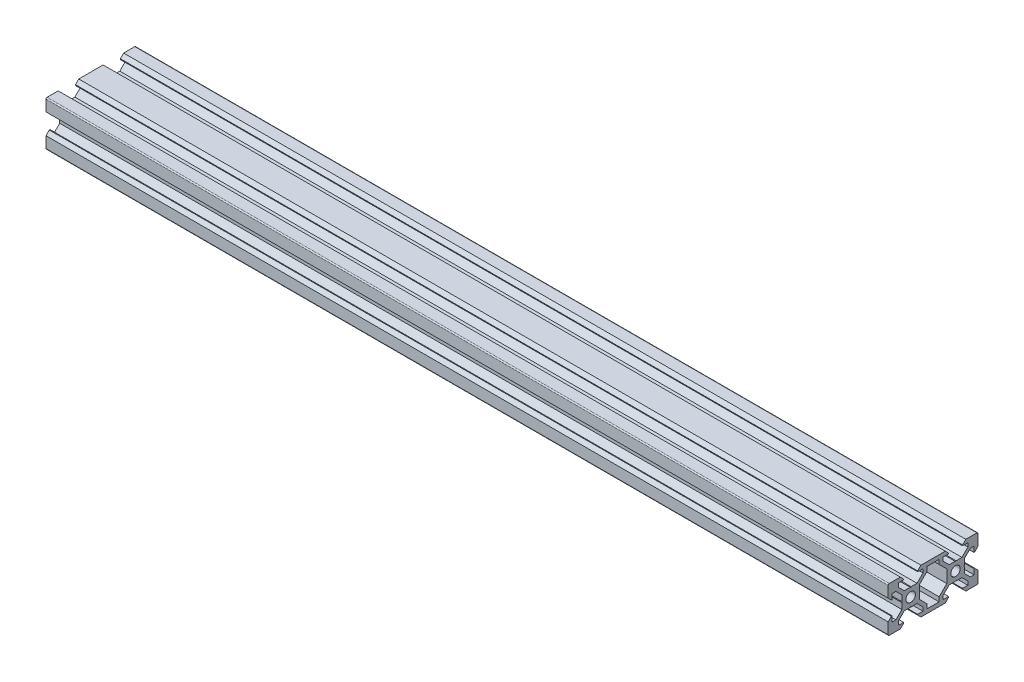
SolidWorks part; units mm, degrees
material "6061-T6 (SS)"
ref_plane "Top" through (0, 0, 0) normal (0, 0, 1) x (1, 0, 0)
ref_plane "Front" through (0, 0, 0) normal (0, 1, 0) x (1, 0, 0)
ref_plane "Right" through (0, 0, 0) normal (1, 0, 0) x (0, 0, -1)
sketch "Profile Sketch" plane through (0, 0, 0) normal (1, 0, 0) x (0, 0, -1)
  line L0 (5.42, 10) -> (-5.42, 10)
  line L1 (-4.5, 8.2) -> (-4.5, 6.56)
  line L2 (-4.5, 6.56) -> (-7.16, 3.9)
  line L3 (-7.16, 3.9) -> (-9.79, 3.9)
  line L4 (-9.79, 3.9) -> (-10, 3.69)
  line L5 (2.7, 8.2) -> (-2.7, 8.2)
  line L6 (-2.7, 8.2) -> (-2.7, 6.2387)
  line L7 (-2.7, 6.2387) -> (-6.1, 2.8387)
  line L8 (-6.1, 2.8387) -> (-6.1, -0.21)
  line L9 (-6.875, 8.545) -> (-6.875, 8.2)
  line L10 (-6.875, 8.2) -> (-4.5, 8.2)
  line L11 (-6.875, 8.545) -> (-5.42, 10)
  line L12 (0, -10) -> (0, 10) construction
  line L13 (-20, 0) -> (20, 0) construction
  line L14 (-10, -10) -> (-10, 10) construction
  line L15 (-6.875, -8.545) -> (-5.42, -10)
  line L16 (-6.875, -8.2) -> (-4.5, -8.2)
  line L17 (-6.875, -8.545) -> (-6.875, -8.2)
  line L18 (-2.7, -6.2387) -> (-6.1, -2.8387)
  line L19 (-2.7, -8.2) -> (-2.7, -6.2387)
  line L20 (2.7, -8.2) -> (-2.7, -8.2)
  line L21 (-7.16, -3.9) -> (-9.79, -3.9)
  line L22 (-4.5, -6.56) -> (-7.16, -3.9)
  line L23 (-4.5, -8.2) -> (-4.5, -6.56)
  line L24 (5.42, -10) -> (-5.42, -10)
  line L25 (-10, 0) -> (-20, 10) construction
  line L26 (-18.545, 3.125) -> (-18.2, 3.125)
  line L27 (-13.125, -8.545) -> (-13.125, -8.2)
  line L28 (-13.125, -8.2) -> (-15.5, -8.2)
  line L29 (-13.125, -8.545) -> (-14.58, -10)
  line L30 (-15.5, -8.2) -> (-15.5, -6.56)
  line L31 (-15.5, -6.56) -> (-12.84, -3.9)
  line L32 (-12.84, -3.9) -> (-10.21, -3.9)
  line L33 (-20, 4.58) -> (-20, 9.5)
  line L34 (-13.9, 2.8387) -> (-13.9, 0.21)
  line L35 (-16.56, 5.5) -> (-13.9, 2.8387)
  line L36 (-12.84, 3.9) -> (-10.21, 3.9)
  line L37 (-15.5, 6.56) -> (-12.84, 3.9)
  line L38 (-15.5, 8.2) -> (-15.5, 6.56)
  line L39 (-13.125, 8.545) -> (-14.58, 10)
  line L40 (-13.125, 8.2) -> (-15.5, 8.2)
  line L41 (-13.125, 8.545) -> (-13.125, 8.2)
  line L42 (-18.2, 3.125) -> (-18.2, 5.5)
  line L43 (-18.545, 3.125) -> (-20, 4.58)
  line L44 (-18.2, 5.5) -> (-16.56, 5.5)
  line L45 (-14.58, 10) -> (-19.5, 10)
  line L46 (-16.56, -5.5) -> (-13.9, -2.8387)
  line L47 (-14.58, -10) -> (-19.5, -10)
  line L48 (-18.2, -5.5) -> (-16.56, -5.5)
  line L49 (-18.545, -3.125) -> (-20, -4.58)
  line L50 (-18.2, -3.125) -> (-18.2, -5.5)
  line L51 (-20, -4.58) -> (-20, -9.5)
  line L52 (-18.545, -3.125) -> (-18.2, -3.125)
  line L53 (10, -10) -> (10, 10) construction
  line L54 (18.545, -3.125) -> (18.2, -3.125)
  line L55 (20, -4.58) -> (20, -9.5)
  line L56 (18.2, -3.125) -> (18.2, -5.5)
  line L57 (18.545, -3.125) -> (20, -4.58)
  line L58 (18.2, -5.5) -> (16.56, -5.5)
  line L59 (14.58, -10) -> (19.5, -10)
  line L60 (16.56, -5.5) -> (13.9, -2.8387)
  line L61 (14.58, 10) -> (19.5, 10)
  line L62 (18.2, 5.5) -> (16.56, 5.5)
  line L63 (18.545, 3.125) -> (20, 4.58)
  line L64 (18.2, 3.125) -> (18.2, 5.5)
  line L65 (13.125, 8.545) -> (13.125, 8.2)
  line L66 (13.125, 8.2) -> (15.5, 8.2)
  line L67 (13.125, 8.545) -> (14.58, 10)
  line L68 (15.5, 8.2) -> (15.5, 6.56)
  line L69 (15.5, 6.56) -> (12.84, 3.9)
  line L70 (12.84, 3.9) -> (10.21, 3.9)
  line L71 (16.56, 5.5) -> (13.9, 2.8387)
  line L72 (13.9, 2.8387) -> (13.9, 0.21)
  line L73 (20, 4.58) -> (20, 9.5)
  line L74 (12.84, -3.9) -> (10.21, -3.9)
  line L75 (15.5, -6.56) -> (12.84, -3.9)
  line L76 (15.5, -8.2) -> (15.5, -6.56)
  line L77 (13.125, -8.545) -> (14.58, -10)
  line L78 (13.125, -8.2) -> (15.5, -8.2)
  line L79 (13.125, -8.545) -> (13.125, -8.2)
  line L80 (18.545, 3.125) -> (18.2, 3.125)
  line L81 (4.5, -8.2) -> (4.5, -6.56)
  line L82 (4.5, -6.56) -> (7.16, -3.9)
  line L83 (7.16, -3.9) -> (9.79, -3.9)
  line L84 (2.7, -8.2) -> (2.7, -6.2387)
  line L85 (2.7, -6.2387) -> (6.1, -2.8387)
  line L86 (6.875, -8.545) -> (6.875, -8.2)
  line L87 (6.875, -8.2) -> (4.5, -8.2)
  line L88 (6.875, -8.545) -> (5.42, -10)
  line L89 (6.875, 8.545) -> (5.42, 10)
  line L90 (6.875, 8.2) -> (4.5, 8.2)
  line L91 (6.875, 8.545) -> (6.875, 8.2)
  line L92 (6.1, 2.8387) -> (6.1, -0.21)
  line L93 (2.7, 6.2387) -> (6.1, 2.8387)
  line L94 (2.7, 8.2) -> (2.7, 6.2387)
  line L95 (9.79, 3.9) -> (10, 3.69)
  line L96 (7.16, 3.9) -> (9.79, 3.9)
  line L97 (4.5, 6.56) -> (7.16, 3.9)
  line L98 (4.5, 8.2) -> (4.5, 6.56)
  line L99 (-10, 3.69) -> (-10.21, 3.9)
  line L100 (-10, -3.69) -> (-10.21, -3.9)
  line L101 (-9.79, -3.9) -> (-10, -3.69)
  line L102 (-13.9, -0.21) -> (-13.69, 0)
  line L103 (-13.69, 0) -> (-13.9, 0.21)
  line L104 (-13.9, -0.21) -> (-13.9, -2.8387)
  line L105 (-6.1, -0.21) -> (-6.31, 0)
  line L106 (-6.31, 0) -> (-6.1, -0.21)
  line L107 (-6.1, -0.21) -> (-6.1, -2.8387)
  line L108 (6.31, 0) -> (6.1, -0.21)
  line L109 (6.1, -0.21) -> (6.31, 0)
  line L110 (13.69, 0) -> (13.9, 0.21)
  line L111 (13.9, -0.21) -> (13.69, 0)
  line L112 (9.79, -3.9) -> (10, -3.69)
  line L113 (10, -3.69) -> (10.21, -3.9)
  line L114 (10, 3.69) -> (10.21, 3.9)
  line L115 (6.1, -0.21) -> (6.1, -2.8387)
  line L116 (13.9, -0.21) -> (13.9, -2.8387)
  line L118 (20, -10) -> (20, 10) construction
  line L119 (20, -10) -> (-20, -10) construction
  line L120 (-20, -10) -> (-20, 10) construction
  line L121 (20, 10) -> (-20, 10) construction
  line L122 (20, -10) -> (-20, 10) construction
  line L123 (-20, -10) -> (20, 10) construction
  circle A0 centre (-10, 0) radius 2.1
  arc A1 (-19.5, 10) -> (-20, 9.5) centre (-19.5, 9.5) ccw
  arc A2 (-19.5, -10) -> (-20, -9.5) centre (-19.5, -9.5) cw
  arc A3 (19.5, -10) -> (20, -9.5) centre (19.5, -9.5) ccw
  arc A4 (19.5, 10) -> (20, 9.5) centre (19.5, 9.5) cw
  circle A5 centre (10, 0) radius 2.1
  point P35 (-2.4957, 0)
  point P108 (0, -8.2)
  point P119 (0, 8.2)
  point P123 (2.4957, 0)
  point P131 (0, 0)
  point P143 (0, 0)
  dimension "D4" = 5.42
  dimension "D5" = 40
  dimension "D6" = 4.2
  dimension "D16" = 0.5
  dimension "D1" = 0.21
  dimension "D2" = 45
  dimension "D3" = 20
  dimension "D7" = 1.5
  dimension "D8" = 1.8
  dimension "D9" = 10
  dimension "D10" = 3.9
  dimension "D11" = 3.9
  dimension "D12" = 1.8
  dimension "D13" = 3.125
  dimension "D14" = 5.5
  dimension "D15" = 1.64
  dimension "D17" = 5.4
extrude "Profile Extrude" add sketch "Profile Sketch" along normal blind 375 contours A4 L61 L67 L65 L66 L68 L69 L70 L114 L95 L96 L97 L98 L90 L91 L89 L0 L11 L9 L10 L1 L2 L3 L4 L99 L36 L37 L38 L40 L41 L39 L45 A1 L33 L43 L26 L42 L44 L35 L34 L103 L102 L104 L46 L48 L50 L52 L49 L51 A2 L47 region at (0, 8.9563, -5.8313)
equation "\"M2x0.4_Close_Hole\"= 2.2"
equation "\"M2.5x0.45_Close_Hole\"= 2.7"
equation "\"M3x0.5_Close_Hole\"= 3.2"
equation "\"M4x0.7_Close_Hole\"= 4.3"
equation "\"M5x0.8_Close_Hole\"= 5.3"
equation "\"M6x1_Close_Hole\"= 6.3"
equation "\"M7x1_Close_Hole\"= 7.4"
equation "\"M8x1.25_Close_Hole\"= 8.4"
equation "\"M2x0.4_Tap_Hole_75\"= 1.6"
equation "\"M3x0.5_Tap_Hole_75\"= 2.5"
equation "\"M4x0.7_Tap_Hole_75\"= 3.3"
equation "\"M5x0.8_Tap_Hole_75\"= 4.2"
equation "\"M6x1_Tap_Hole_75\"= 5"
equation "\"M7x1_Tap_Hole_75\"= 6"
equation "\"M8x1.25_Tap_Hole_75\"= 6.8"
